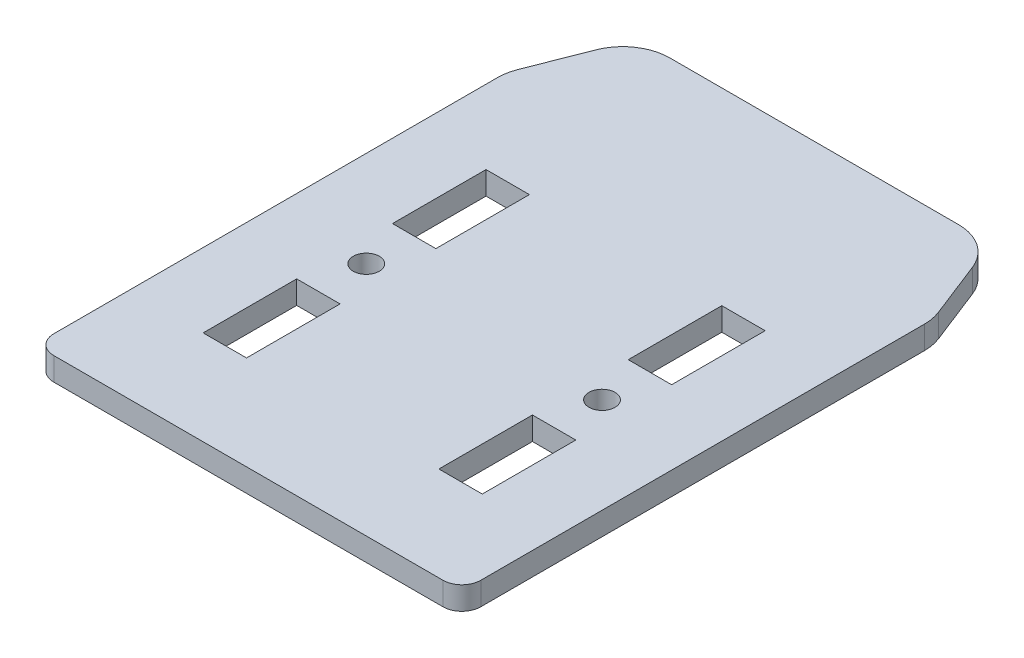
SolidWorks part; units mm, degrees
ref_plane "Front Plane" through (0, 0, 0) normal (0, 0, 1) x (1, 0, 0)
ref_plane "Top Plane" through (0, 0, 0) normal (0, 1, 0) x (1, 0, 0)
ref_plane "Right Plane" through (0, 0, 0) normal (1, 0, 0) x (0, 0, -1)
sketch "Sketch1" plane through (0, 0, 0) normal (0, 1, 0) x (1, 0, 0)
  line L0 (12.954, 0) -> (-12.954, 0) construction
  line L1 (12.954, -50.8) -> (-12.954, -50.8)
  line L2 (12.954, -25.4) -> (12.954, -12.8)
  line L3 (12.954, 50.8) -> (-12.954, 50.8)
  line L5 (12.954, -50.8) -> (-12.954, 50.8) construction
  line L6 (12.954, 50.8) -> (-12.954, -50.8) construction
  line L7 (0, -50.8) -> (0, 50.8) construction
  line L8 (-12.954, -6.35) -> (12.954, -6.35) construction
  line L9 (18.796, -12.8) -> (12.954, -12.8)
  line L10 (18.796, -12.8) -> (18.796, -25.4)
  line L11 (18.796, 0.1) -> (12.954, 0.1)
  line L12 (-18.796, 0.1) -> (-12.954, -12.8) construction
  line L13 (18.796, -12.8) -> (12.954, 0.1) construction
  line L14 (18.796, 0.1) -> (12.954, -12.8) construction
  line L15 (12.954, 0) -> (12.954, 12.7)
  line L16 (12.954, -25.4) -> (18.796, -25.4)
  line L17 (-18.796, -12.8) -> (-12.954, 0.1) construction
  line L18 (12.954, -50.8) -> (16.0528, -50.8)
  line L19 (-12.954, 0) -> (-12.954, 0.1)
  line L20 (12.954, 12.7) -> (18.796, 12.7)
  line L21 (-28.7528, 50.8) -> (-28.7528, -50.8)
  line L22 (12.954, 50.8) -> (16.0528, 50.8)
  line L23 (-16.0528, -50.8) -> (-28.7528, -50.8)
  line L24 (16.0528, 50.8) -> (28.7528, 50.8)
  line L25 (18.796, 12.7) -> (18.796, 0.1)
  line L26 (16.0528, -50.8) -> (28.7528, -50.8)
  line L27 (28.7528, 50.8) -> (28.7528, -50.8)
  line L28 (12.954, 0) -> (12.954, 0.1)
  line L29 (-18.796, 12.7) -> (-18.796, 0.1)
  line L30 (-16.0528, 50.8) -> (-28.7528, 50.8)
  line L31 (-12.954, 50.8) -> (-16.0528, 50.8)
  line L32 (-12.954, 12.7) -> (-18.796, 12.7)
  line L33 (-12.954, -50.8) -> (-16.0528, -50.8)
  line L34 (-12.954, -25.4) -> (-18.796, -25.4)
  line L35 (-12.954, 0) -> (-12.954, 0.1)
  line L36 (-18.796, 0.1) -> (-12.954, 0.1)
  line L37 (-18.796, -12.8) -> (-18.796, -25.4)
  line L38 (-18.796, -12.8) -> (-12.954, -12.8)
  line L39 (-12.954, 0) -> (-12.954, 12.7)
  line L40 (-12.954, 0) -> (-12.954, 0.1)
  line L41 (-12.954, -12.8) -> (-12.954, -25.4)
  point P0 (0, 0)
  point P10 (15.875, -6.35)
  point P37 (-15.875, -6.35)
  dimension "D1" = 25.908
  dimension "D2" = 101.6
  dimension "D3" = 5.842
  dimension "D4" = 44.45
  dimension "D5" = 12.9
  dimension "D6" = 19.05
  dimension "D7" = 19.05
  dimension "D8" = 12.7
extrude "Boss-Extrude1" add sketch "Sketch1" along normal blind 3.0988 contours L38 L41 L1 L18 L26 L27 L24 L22 L3 L31 L30 L21 L23 L33 L34 L37 L39 L36 L29 L32 L16 L2 L9 L10 L20 L25 L11 L15 region at (0, 0, -0.337)
sketch "Sketch2" plane through (0, 3.0988, 0) normal (0, 1, 0) x (1, 0, 0)
  line L0 (-15.875, 0.1) -> (-15.875, -12.8) construction
  line L1 (-18.796, 0.1) -> (-12.954, 0.1) construction
  line L2 (-18.796, -12.8) -> (-12.954, -12.8) construction
  line L3 (15.875, -12.8) -> (15.875, 0.1) construction
  line L4 (18.796, -12.8) -> (12.954, -12.8) construction
  line L5 (18.796, 0.1) -> (12.954, 0.1) construction
  line L6 (-18.796, -50.8) -> (-28.7528, -38.1)
  line L7 (28.7528, -50.8) -> (-28.7528, -50.8) construction
  line L8 (-28.7528, 50.8) -> (-28.7528, -50.8) construction
  line L9 (0, 50.8) -> (0, -50.8) construction
  line L10 (15.875, 0.1) -> (15.875, -12.8) construction
  line L11 (28.7528, -50.8) -> (18.796, -50.8)
  line L12 (-28.7528, 25.4) -> (-18.796, 50.8)
  line L13 (-28.7528, 50.8) -> (28.7528, 50.8) construction
  line L14 (28.7528, -38.1) -> (28.7528, -50.8)
  line L15 (-28.7528, 25.4) -> (-28.7528, 50.8)
  line L16 (-28.7528, 50.8) -> (-18.796, 50.8)
  line L17 (-28.7528, -38.1) -> (-28.7528, -50.8)
  line L18 (-28.7528, -50.8) -> (-18.796, -50.8)
  line L19 (28.7528, 50.8) -> (18.796, 50.8)
  line L20 (28.7528, 25.4) -> (28.7528, 50.8)
  line L21 (28.7528, 25.4) -> (18.796, 50.8)
  line L22 (18.796, -50.8) -> (28.7528, -38.1)
  circle A0 centre (-15.875, -6.35) radius 1.7526
  circle A1 centre (15.875, -6.35) radius 1.7526
  circle A2 centre (15.875, -6.35) radius 1.7526
  line M12 (-28.7528, -50.8) -> (28.7528, -50.8)
  line M13 (28.7528, -50.8) -> (28.7528, 50.8)
  line M14 (28.7528, 50.8) -> (-28.7528, 50.8)
  line M15 (-28.7528, 50.8) -> (-28.7528, -50.8)
  dimension "D1" = 3.5052
  dimension "D2" = 3.5052
extrude "Cut-Extrude1" cut sketch "Sketch2" against normal through all contours A0 | A1 | L21 M13 M14 | L22 M12 M13 | L6 M12 M15 | L12 M15 M14 region at (-25.4339, 3.0988, 46.5667) region at (25.4339, 3.0988, 46.5667) region at (-25.4339, 3.0988, -42.3333) region at (25.4339, 3.0988, -42.3333) region at (-15.875, 3.0988, 6.35) region at (15.875, 3.0988, 6.35)
fillet "Fillet1" radius 6.35 8 edges at (18.796, 1.5494, 50.8) (-18.796, 1.5494, 50.8) (-28.7528, 1.5494, 38.1) (-28.7528, 1.5494, -25.4) (-18.796, 1.5494, -50.8) (18.796, 1.5494, -50.8) (28.7528, 1.5494, -25.4) (28.7528, 1.5494, 38.1)
sketch "Sketch3" plane through (0, 0, 0) normal (0, -1, 0) x (-1, 0, 0)
  line L0 (-28.7528, 24.1999) -> (-28.7528, -35.9075) construction
  line L1 (-28.7528, -38.1) -> (30.0824, -38.1)
  line L2 (-28.7528, -38.1) -> (-28.7528, -50.8)
  line L3 (-28.7528, -50.8) -> (30.0824, -50.8)
  line L4 (30.0824, -38.1) -> (30.0824, -50.8)
  line L5 (-15.7055, -50.8) -> (15.7055, -50.8) construction
  dimension "D1" = 12.7
extrude "Cut-Extrude2" cut sketch "Sketch3" against normal through all
fillet "Fillet2" radius 2.54 2 edges at (-28.3623, 1.5494, 38.1) (28.3623, 1.5494, 38.1)
sketch "Sketch4" plane through (0, 0, 0) normal (0, -1, 0) x (-1, 0, 0)
  line L0 (14.4647, 50.8) -> (-14.4647, 50.8) construction
  line L1 (-35.2772, 38.1) -> (41.6124, 38.1)
  line L2 (-35.2772, 38.1) -> (-35.2772, 50.8)
  line L3 (-35.2772, 50.8) -> (41.6124, 50.8)
  line L4 (41.6124, 38.1) -> (41.6124, 50.8)
  dimension "D1" = 12.7
extrude "Cut-Extrude3" cut sketch "Sketch4" against normal through all
fillet "Fillet3" radius 6.35 2 edges at (23.7744, 1.5494, -38.1) (-23.7744, 1.5494, -38.1)
